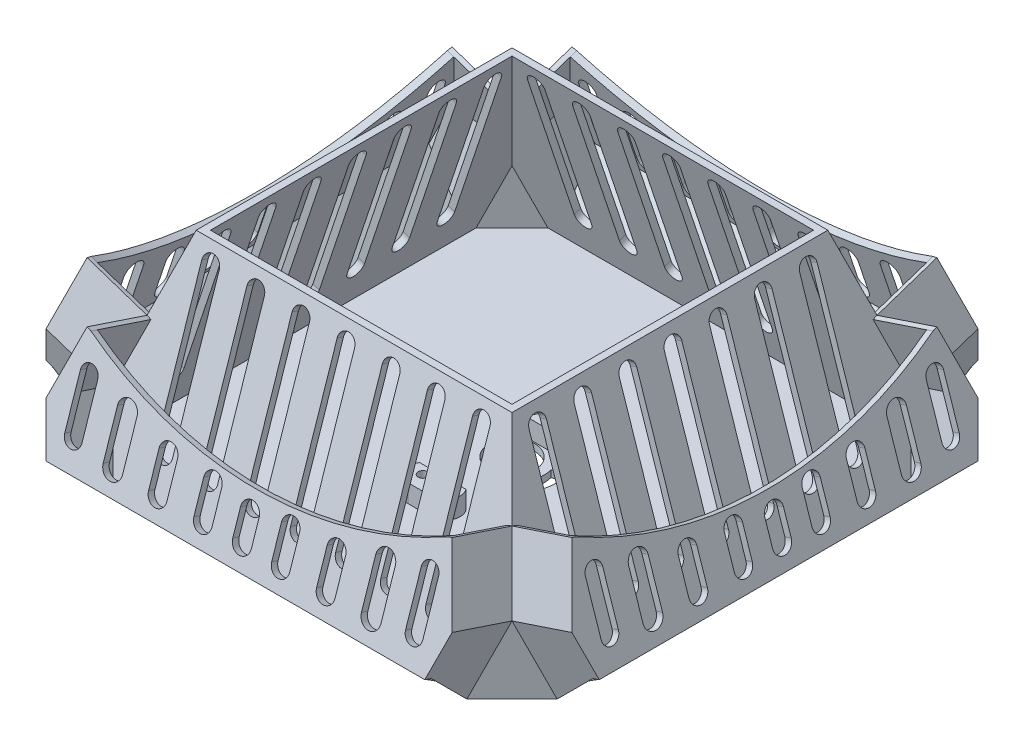
SolidWorks part; units mm, degrees
ref_plane "前视基准面" through (0, 0, 0) normal (0, 0, 1) x (1, 0, 0)
ref_plane "上视基准面" through (0, 0, 0) normal (0, 1, 0) x (1, 0, 0)
ref_plane "右视基准面" through (0, 0, 0) normal (1, 0, 0) x (0, 0, -1)
other "Configuration Table"
sketch "草图1" plane through (0, 0, 0) normal (0, 1, 0) x (1, 0, 0)
  line L1 (-70, 70) -> (70, 70)
  line L2 (-70, 70) -> (-70, -70)
  line L3 (-70, -70) -> (70, -70)
  line L4 (70, 70) -> (70, -70)
  line L5 (-70, 70) -> (70, -70) construction
  line L6 (-70, -70) -> (70, 70) construction
  point P0 (0, 0)
  dimension "D1" = 140
  dimension "D2" = 140
ref_plane "基准面1" through (0, -90, 0) normal (0, 1, 0) x (1, 0, 0)
sketch "草图2" plane through (0, -90, 0) normal (0, 1, 0) x (1, 0, 0)
  line L0 (70, 70) -> (70, -70) construction
  line L1 (-100, -100) -> (100, -100)
  line L2 (-100, -100) -> (-100, 100)
  line L3 (-100, 100) -> (100, 100)
  line L4 (100, -100) -> (100, 100)
  line L5 (-100, -100) -> (100, 100) construction
  line L6 (-100, 100) -> (100, -100) construction
  line L7 (-70, -70) -> (70, -70) construction
  point P0 (0, 0)
  dimension "D1" = 30
  dimension "D2" = 30
loft "放样1" add profiles "草图2", "草图1" connector at (-100, -90, -100) connector at (-70, 0, -70)
sketch "草图4" plane through (0, 0, 0) normal (0, 1, 0) x (1, 0, 0)
  line L0 (-80, 100) -> (-100, 80)
  line L1 (-100, 100) -> (100, 100) construction
  line L2 (-100, -100) -> (-100, 100) construction
  line L3 (-100, 80) -> (-100, 100)
  line L4 (-100, 100) -> (-80, 100)
  line L5 (100, 80) -> (80, 100)
  line L6 (80, 100) -> (100, 100)
  line L7 (100, 100) -> (100, 80)
  line L8 (80, -100) -> (100, -80)
  line L9 (100, -80) -> (100, -100)
  line L10 (100, -100) -> (80, -100)
  line L11 (-100, -80) -> (-80, -100)
  line L12 (-80, -100) -> (-100, -100)
  line L13 (-100, -100) -> (-100, -80)
  point P20 (0, 0)
  dimension "D1" = 45
  dimension "D2" = 20
  dimension "D3" = 4
extrude "切除-拉伸1" cut sketch "草图4" against normal blind 128
shell "抽壳2" thickness 3 removed face at (0, 0, 0)
sketch "草图6" plane through (0, 21, -63) normal (0, 0.3162, -0.9487) x (-1, 0, 0)
  line L0 (-90, -85.3815) -> (-80, -117.0043)
  line L1 (-80, -117.0043) -> (-76.8536, -117.0043)
  line L2 (-80, -117.0043) -> (80, -117.0043) construction
  line L3 (-76.8536, -117.0043) -> (-88.4268, -80.4066)
  line L4 (-90, -85.3815) -> (-70, -22.1359) construction
  line L5 (-88.4268, -80.4066) -> (-90, -85.3815)
  line L6 (90, -85.3815) -> (80, -117.0043)
  line L7 (80, -117.0043) -> (76.8536, -117.0043)
  line L8 (76.8536, -117.0043) -> (88.4268, -80.4066)
  line L9 (90, -85.3815) -> (70, -22.1359) construction
  line L10 (88.4268, -80.4066) -> (90, -85.3815)
  dimension "D1" = 3
  dimension "D2" = 3
extrude "凸台-拉伸1" add sketch "草图6" along normal blind 25
sketch "草图7" plane through (-63, 21, 0) normal (-0.9487, 0.3162, 0) x (0, 0, 1)
  line L0 (-80, -117.0043) -> (-90, -85.3815)
  line L1 (-90, -85.3815) -> (-88.4268, -80.4066)
  line L2 (-88.4268, -80.4066) -> (-70, -22.1359) construction
  line L3 (-88.4268, -80.4066) -> (-76.8536, -117.0043)
  line L4 (-80, -117.0043) -> (80, -117.0043) construction
  line L5 (-76.8536, -117.0043) -> (-80, -117.0043)
  line L6 (80, -117.0043) -> (90, -85.3815)
  line L7 (80, -117.0043) -> (90, -85.3815) construction
  line L8 (80, -117.0043) -> (100, -110.6797) construction
  line L9 (90, -85.3815) -> (100, -110.6797) construction
  line L10 (90, -85.3815) -> (88.4268, -80.4066)
  line L11 (90, -85.3815) -> (70, -22.1359) construction
  line L12 (88.4268, -80.4066) -> (76.8536, -117.0043)
  line L13 (76.8536, -117.0043) -> (80, -117.0043)
  dimension "D1" = 3
  dimension "D2" = 3
extrude "凸台-拉伸2" add sketch "草图7" along normal blind 25
sketch "草图8" plane through (0, 21, 63) normal (0, 0.3162, 0.9487) x (1, 0, 0)
  line L0 (-90, -85.3815) -> (-80, -117.0043)
  line L1 (-80, -117.0043) -> (-76.8536, -117.0043)
  line L2 (-80, -117.0043) -> (80, -117.0043) construction
  line L3 (-76.8536, -117.0043) -> (-88.4268, -80.4066)
  line L4 (-88.4268, -80.4066) -> (-70, -22.1359) construction
  line L5 (-88.4268, -80.4066) -> (-90, -85.3815)
  line L6 (90, -85.3815) -> (80, -117.0043)
  line L7 (80, -117.0043) -> (76.8536, -117.0043)
  line L8 (76.8536, -117.0043) -> (88.4268, -80.4066)
  line L9 (90, -85.3815) -> (70, -22.1359) construction
  line L10 (88.4268, -80.4066) -> (90, -85.3815)
  dimension "D1" = 3
  dimension "D2" = 3
extrude "凸台-拉伸3" add sketch "草图8" along normal blind 25
sketch "草图9" plane through (63, 21, 0) normal (0.9487, 0.3162, 0) x (0, 0, -1)
  line L0 (-90, -85.3815) -> (-80, -117.0043)
  line L1 (-80, -117.0043) -> (-76.8536, -117.0043)
  line L2 (-80, -117.0043) -> (80, -117.0043) construction
  line L3 (-76.8536, -117.0043) -> (-88.4268, -80.4066)
  line L4 (-88.4268, -80.4066) -> (-70, -22.1359) construction
  line L5 (-88.4268, -80.4066) -> (-90, -85.3815)
  line L6 (80, -117.0043) -> (90, -85.3815)
  line L7 (90, -85.3815) -> (88.4268, -80.4066)
  line L8 (88.4268, -80.4066) -> (70, -22.1359) construction
  line L9 (88.4268, -80.4066) -> (76.8536, -117.0043)
  line L10 (76.8536, -117.0043) -> (80, -117.0043)
  dimension "D1" = 3
  dimension "D2" = 3
extrude "凸台-拉伸4" add sketch "草图9" along normal blind 25
sketch "草图11" plane through (0, 0, 0) normal (0, 0, 1) x (1, 0, 0)
  line L0 (-100, -90) -> (-128.5669, -61.4331)
  line L1 (-128.5669, -61.4331) -> (-128.5669, -90)
  line L2 (110.0001, -90) -> (-110.0001, -90) construction
  line L3 (-128.5669, -90) -> (-100, -90)
  dimension "D1" = 45
extrude "切除-拉伸2" cut sketch "草图11" against normal mid plane 260
sketch "草图12" plane through (0, 0, 0) normal (1, 0, 0) x (0, 0, -1)
  line L0 (-100, -90) -> (-128.7607, -61.2393)
  line L1 (110.0001, -90) -> (-110.0001, -90) construction
  line L2 (-100, -90) -> (-90, -60) construction
  line L3 (-128.7607, -61.2393) -> (-128.7607, -90)
  line L4 (-128.7607, -90) -> (-100, -90)
  line L5 (0, 15.5887) -> (0, -110.0855) construction
  line L6 (128.7607, -90) -> (100, -90)
  line L7 (128.7607, -61.2393) -> (128.7607, -90)
  line L8 (100, -90) -> (128.7607, -61.2393)
  dimension "D1" = 45
extrude "切除-拉伸3" cut sketch "草图12" against normal mid plane 260
sketch "草图13" plane through (0, 0, 0) normal (0, 0, 1) x (1, 0, 0)
  line L0 (100, -90) -> (131.318, -58.682)
  line L1 (131.318, -58.682) -> (131.318, -90)
  line L2 (110.0001, -90) -> (-110.0001, -90) construction
  line L3 (131.318, -90) -> (100, -90)
  dimension "D1" = 45
extrude "切除-拉伸4" cut sketch "草图13" against normal mid plane 260
sketch "草图14" plane through (0, -87, 0) normal (0, 1, 0) x (1, 0, 0)
  circle A0 centre (0, 0) radius 3.5
  dimension "D1" = 7
extrude "切除-拉伸5" cut sketch "草图14" against normal mid plane 260
sketch "草图17" plane through (0, 0, 0) normal (1, 0, 0) x (0, 0, -1)
  line L0 (-119.7642, -70.2358) -> (-100, -90)
  line L1 (110.0001, -90) -> (-110.0001, -90) construction
  line L2 (-119.7642, -70.2358) -> (-100, -90) construction
  line L3 (-100, -90) -> (-98.9393, -86.818)
  line L4 (-100, -90) -> (-90, -60) construction
  line L5 (-98.9393, -86.818) -> (-118.7036, -67.0538)
  line L6 (-119.7642, -70.2358) -> (-113.7171, -52.0943) construction
  line L7 (-118.7036, -67.0538) -> (-119.7642, -70.2358)
  line L8 (0, 20.2497) -> (0, -104.6835) construction
  line L9 (118.7036, -67.0538) -> (119.7642, -70.2358)
  line L10 (98.9393, -86.818) -> (118.7036, -67.0538)
  line L11 (100, -90) -> (98.9393, -86.818)
  line L12 (119.7642, -70.2358) -> (100, -90)
  dimension "D1" = 3
extrude "凸台-拉伸8" add sketch "草图17" along normal up to next and the other way up to next
sketch "草图18" plane through (0, 0, 0) normal (0, 0, 1) x (1, 0, 0)
  line L0 (-119.7642, -70.2358) -> (-100, -90)
  line L1 (-100, -90) -> (-98.9393, -86.818)
  line L2 (-100, -90) -> (-90, -60) construction
  line L3 (-98.9393, -86.818) -> (-118.7036, -67.0538)
  line L4 (-119.7642, -70.2358) -> (-113.7171, -52.0943) construction
  line L5 (-118.7036, -67.0538) -> (-119.7642, -70.2358)
  line L6 (0, 15.1419) -> (0, -105.5441) construction
  line L7 (118.7036, -67.0538) -> (119.7642, -70.2358)
  line L8 (98.9393, -86.818) -> (118.7036, -67.0538)
  line L9 (100, -90) -> (98.9393, -86.818)
  line L10 (119.7642, -70.2358) -> (100, -90)
  dimension "D1" = 3
extrude "凸台-拉伸9" add sketch "草图18" along normal up to next and the other way up to next
sketch "草图20" plane through (0, -87, 0) normal (0, 1, 0) x (1, 0, 0)
  circle A0 centre (0, 0) radius 10.1
  dimension "D1" = 20.2
extrude "切除-拉伸6" cut sketch "草图20" against normal blind 26
sketch "草图22" plane through (63, 21, 0) normal (0.9487, 0.3162, 0) x (0, 0, -1)
  line L0 (-61.1056, -30.1412) -> (-61.1056, -95.5093) construction
  line L1 (-57.2442, -30.1412) -> (-57.2442, -95.5093)
  line L2 (-64.967, -30.1412) -> (-64.967, -95.5093)
  line L3 (-41.1056, -30.1412) -> (-41.1056, -95.5093) construction
  line L4 (-37.2442, -30.1412) -> (-37.2442, -95.5093)
  line L5 (-44.967, -30.1412) -> (-44.967, -95.5093)
  line L6 (-21.1056, -30.1412) -> (-21.1056, -95.5093) construction
  line L7 (-17.2442, -30.1412) -> (-17.2442, -95.5093)
  line L8 (-24.967, -30.1412) -> (-24.967, -95.5093)
  line L9 (-1.1056, -30.1412) -> (-1.1056, -95.5093) construction
  line L10 (2.7558, -30.1412) -> (2.7558, -95.5093)
  line L11 (-4.967, -30.1412) -> (-4.967, -95.5093)
  line L12 (18.8944, -30.1412) -> (18.8944, -95.5093) construction
  line L13 (22.7558, -30.1412) -> (22.7558, -95.5093)
  line L14 (15.033, -30.1412) -> (15.033, -95.5093)
  line L15 (38.8944, -30.1412) -> (38.8944, -95.5093) construction
  line L16 (42.7558, -30.1412) -> (42.7558, -95.5093)
  line L17 (35.033, -30.1412) -> (35.033, -95.5093)
  line L18 (58.8944, -30.1412) -> (58.8944, -95.5093) construction
  line L19 (62.7558, -30.1412) -> (62.7558, -95.5093)
  line L20 (55.033, -30.1412) -> (55.033, -95.5093)
  arc A0 (-57.2442, -30.1412) -> (-64.967, -30.1412) centre (-61.1056, -30.1412) ccw
  arc A1 (-64.967, -95.5093) -> (-57.2442, -95.5093) centre (-61.1056, -95.5093) ccw
  arc A2 (-37.2442, -30.1412) -> (-44.967, -30.1412) centre (-41.1056, -30.1412) ccw
  arc A3 (-44.967, -95.5093) -> (-37.2442, -95.5093) centre (-41.1056, -95.5093) ccw
  arc A4 (-17.2442, -30.1412) -> (-24.967, -30.1412) centre (-21.1056, -30.1412) ccw
  arc A5 (-24.967, -95.5093) -> (-17.2442, -95.5093) centre (-21.1056, -95.5093) ccw
  arc A6 (2.7558, -30.1412) -> (-4.967, -30.1412) centre (-1.1056, -30.1412) ccw
  arc A7 (-4.967, -95.5093) -> (2.7558, -95.5093) centre (-1.1056, -95.5093) ccw
  arc A8 (22.7558, -30.1412) -> (15.033, -30.1412) centre (18.8944, -30.1412) ccw
  arc A9 (15.033, -95.5093) -> (22.7558, -95.5093) centre (18.8944, -95.5093) ccw
  arc A10 (42.7558, -30.1412) -> (35.033, -30.1412) centre (38.8944, -30.1412) ccw
  arc A11 (35.033, -95.5093) -> (42.7558, -95.5093) centre (38.8944, -95.5093) ccw
  arc A12 (62.7558, -30.1412) -> (55.033, -30.1412) centre (58.8944, -30.1412) ccw
  arc A13 (55.033, -95.5093) -> (62.7558, -95.5093) centre (58.8944, -95.5093) ccw
  point P2 (-61.1056, -62.8252)
  point P11 (-41.1056, -62.8252)
  point P18 (-21.1056, -62.8252)
  point P25 (-1.1056, -62.8252)
  point P32 (18.8944, -62.8252)
  point P39 (38.8944, -62.8252)
  point P46 (58.8944, -62.8252)
  dimension "D1" = 7
extrude "切除-拉伸7" cut sketch "草图22" against normal blind 10
pattern_circular "阵列(圆周)2" count 4 every 90 about axis through (0, -87, 0) along (0, 1, 0) of "切除-拉伸7"
sketch "草图26" plane through (0, -87, 0) normal (0, 1, 0) x (1, 0, 0)
  circle A0 centre (-5, 14.5) radius 2.1
  circle A1 centre (5, 14.5) radius 2.1
  circle A2 centre (-5, -34.5) radius 2.1
  circle A3 centre (5, -34.5) radius 2.1
  dimension "D1" = 4.2
extrude "切除-拉伸10" cut sketch "草图26" against normal blind 10
sketch "草图37" plane through (0, -90, 0) normal (0, -1, 0) x (1, 0, 0)
  circle A0 centre (0, 0) radius 32.5
  circle A1 centre (0, 0) radius 45
  dimension "D1" = 65
  dimension "D2" = 90
extrude "切除-拉伸13" cut sketch "草图37" against normal blind 1
sketch "草图51" plane through (0, -90, 0) normal (0, -1, 0) x (1, 0, 0)
  line L2 (11.2742, 8.4827) -> (15.9244, 11.9814)
  line L3 (13.6163, -3.696) -> (19.2324, -5.2205)
  arc A2 (13.6163, -3.696) -> (11.2742, 8.4827) centre (0, 0) ccw
  arc A3 (19.2324, -5.2205) -> (15.9244, 11.9814) centre (0, 0) ccw
extrude "切除-拉伸14" cut sketch "草图51" against normal blind 10
sketch "草图53" plane through (0, -87, 0) normal (0, 1, 0) x (1, 0, 0)
  line L0 (-5, 14.5) -> (5, 14.5) construction
  line L1 (-5, 21) -> (5, 21)
  line L2 (-5, 8) -> (5, 8)
  line L3 (-5, -34.5) -> (5, -34.5) construction
  line L4 (-5, -28) -> (5, -28)
  line L5 (-5, -41) -> (5, -41)
  arc A0 (-5, 21) -> (-5, 8) centre (-5, 14.5) ccw
  arc A1 (5, 8) -> (5, 21) centre (5, 14.5) ccw
  arc A2 (-5, -28) -> (-5, -41) centre (-5, -34.5) ccw
  arc A3 (5, -41) -> (5, -28) centre (5, -34.5) ccw
  point P4 (0, 14.5)
  point P9 (0, -34.5)
  dimension "D1" = 13
  dimension "D2" = 13
extrude "凸台-拉伸17" add sketch "草图53" along normal blind 8
sketch "草图54" plane through (0, -90, 0) normal (0, -1, 0) x (1, 0, 0)
  circle A0 centre (-5, -14.5) radius 2.1
  circle A1 centre (5, -14.5) radius 2.1
  circle A2 centre (0, 0) radius 10.1
  circle A3 centre (-5, 34.5) radius 2.1
  circle A4 centre (5, 34.5) radius 2.1
extrude "切除-拉伸15" cut sketch "草图54" against normal blind 160
sketch "草图55" plane through (0, -87, 0) normal (0, 1, 0) x (1, 0, 0)
  line L0 (-18.9185, 0) -> (-18.9185, 10.5924)
  line L2 (-18.9185, 0) -> (-18.9185, -30.6798)
  line L3 (-18.9185, -30.6798) -> (17.5542, -30.6798)
  line L4 (17.5542, 0) -> (17.5542, -30.6798)
  line L5 (-18.9185, 10.5924) -> (17.5542, 10.5924)
  line L6 (17.5542, 10.5924) -> (17.5542, 0)
extrude "切除-拉伸16" cut sketch "草图55" along normal blind 160
pattern_circular "阵列(圆周)3" count 4 every 90 about axis through (0, -113, 0) along (0, 1, 0) of "凸台-拉伸8"
sketch "草图57" plane through (-63, 21, 0) normal (-0.9487, 0.3162, 0) x (0, 0, 1)
  line L0 (-88.4268, -80.4066) -> (-80.889, -56.57)
  line L1 (-88.4268, -80.4066) -> (-70, -22.1359) construction
  line L2 (-80.889, -56.57) -> (-78.9821, -57.173)
  line L3 (-78.9821, -57.173) -> (-87.378, -83.7232)
  line L4 (-77.9142, -113.6502) -> (-88.4268, -80.4066) construction
  line L5 (-88.4268, -80.4066) -> (-87.378, -83.7232)
  line L6 (0, -117.0043) -> (0, 49.8751) construction
  line L8 (-76.8536, -117.0043) -> (76.8536, -117.0043) construction
  line L9 (88.4268, -80.4066) -> (87.378, -83.7232)
  line L10 (78.9821, -57.173) -> (87.378, -83.7232)
  line L11 (80.889, -56.57) -> (78.9821, -57.173)
  line L12 (88.4268, -80.4066) -> (80.889, -56.57)
  dimension "D1" = 2
  dimension "D2" = 25
extrude "凸台-拉伸22" add sketch "草图57" along normal blind 25
pattern_circular "阵列(圆周)4" count 4 every 90 about axis through (0, -113, 0) along (0, 1, 0) of "凸台-拉伸22"
sketch "草图58" plane through (0, 28.9057, 86.7171) normal (0, 0.3162, 0.9487) x (1, 0, 0)
  line L0 (-80.889, -56.57) -> (-90, -85.3815)
  line L1 (-90, -85.3815) -> (-83.9528, -104.5043)
  line L2 (-83.9528, -104.5043) -> (83.9528, -104.5043)
  line L3 (83.9528, -104.5043) -> (90, -85.3815)
  line L4 (90, -85.3815) -> (80.889, -56.57)
  line L5 (80.889, -56.57) -> (78.9821, -57.173)
  line L6 (-80.889, -56.57) -> (-78.9821, -57.173)
  line L7 (0, -104.5043) -> (0, -58.3989) construction
  line L8 (0, -84.2936) -> (0, -95.1298) construction
  line L9 (4.1281, -84.2936) -> (4.1281, -95.1298)
  line L10 (-4.1281, -84.2936) -> (-4.1281, -95.1298)
  line L11 (-17.2442, -81.7439) -> (-17.2442, -95.5093) construction
  line L12 (-17.2442, -95.5093) -> (-17.2442, -30.1412) construction
  line L13 (-13.2418, -81.7439) -> (-13.2418, -95.5093)
  line L14 (-21.2466, -81.7439) -> (-21.2466, -95.5093)
  line L15 (-37.2442, -80.7877) -> (-37.2442, -95.5093) construction
  line L16 (-37.2442, -95.5093) -> (-37.2442, -30.1412) construction
  line L17 (-33.1614, -80.7877) -> (-33.1614, -95.5093)
  line L18 (-41.327, -80.7877) -> (-41.327, -95.5093)
  line L19 (-57.2442, -75.0509) -> (-57.2442, -95.1298) construction
  line L20 (-57.2442, -95.5093) -> (-57.2442, -30.1412) construction
  line L21 (-52.9216, -75.0509) -> (-52.9216, -95.1298)
  line L22 (-61.5667, -75.0509) -> (-61.5667, -95.1298)
  line L23 (-75.5503, -70.7283) -> (-75.5503, -92.7395) construction
  line L24 (-71.7257, -70.7283) -> (-71.7257, -92.7395)
  line L25 (-79.3749, -70.7283) -> (-79.3749, -92.7395)
  line L26 (75.5503, -70.7283) -> (75.5503, -92.7395) construction
  line L27 (71.7257, -70.7283) -> (71.7257, -92.7395)
  line L28 (79.3749, -70.7283) -> (79.3749, -92.7395)
  line L29 (57.2442, -75.0509) -> (57.2442, -95.1298) construction
  line L30 (52.9216, -75.0509) -> (52.9216, -95.1298)
  line L31 (61.5667, -75.0509) -> (61.5667, -95.1298)
  line L32 (37.2442, -80.7877) -> (37.2442, -95.5093) construction
  line L33 (33.1614, -80.7877) -> (33.1614, -95.5093)
  line L34 (41.327, -80.7877) -> (41.327, -95.5093)
  line L35 (17.2442, -81.7439) -> (17.2442, -95.5093) construction
  line L36 (13.2418, -81.7439) -> (13.2418, -95.5093)
  line L37 (21.2466, -81.7439) -> (21.2466, -95.5093)
  arc A0 (-78.9821, -57.173) -> (78.9821, -57.173) centre (0, 97.3143) ccw
  arc A1 (4.1281, -84.2936) -> (-4.1281, -84.2936) centre (0, -84.2936) ccw
  arc A2 (-4.1281, -95.1298) -> (4.1281, -95.1298) centre (0, -95.1298) ccw
  arc A3 (-13.2418, -81.7439) -> (-21.2466, -81.7439) centre (-17.2442, -81.7439) ccw
  arc A4 (-21.2466, -95.5093) -> (-13.2418, -95.5093) centre (-17.2442, -95.5093) ccw
  arc A5 (-33.1614, -80.7877) -> (-41.327, -80.7877) centre (-37.2442, -80.7877) ccw
  arc A6 (-41.327, -95.5093) -> (-33.1614, -95.5093) centre (-37.2442, -95.5093) ccw
  arc A7 (-52.9216, -75.0509) -> (-61.5667, -75.0509) centre (-57.2442, -75.0509) ccw
  arc A8 (-61.5667, -95.1298) -> (-52.9216, -95.1298) centre (-57.2442, -95.1298) ccw
  arc A9 (-71.7257, -70.7283) -> (-79.3749, -70.7283) centre (-75.5503, -70.7283) ccw
  arc A10 (-79.3749, -92.7395) -> (-71.7257, -92.7395) centre (-75.5503, -92.7395) ccw
  arc A11 (71.7257, -70.7283) -> (79.3749, -70.7283) centre (75.5503, -70.7283) cw
  arc A12 (79.3749, -92.7395) -> (71.7257, -92.7395) centre (75.5503, -92.7395) cw
  arc A13 (52.9216, -75.0509) -> (61.5667, -75.0509) centre (57.2442, -75.0509) cw
  arc A14 (61.5667, -95.1298) -> (52.9216, -95.1298) centre (57.2442, -95.1298) cw
  arc A15 (33.1614, -80.7877) -> (41.327, -80.7877) centre (37.2442, -80.7877) cw
  arc A16 (41.327, -95.5093) -> (33.1614, -95.5093) centre (37.2442, -95.5093) cw
  arc A17 (13.2418, -81.7439) -> (21.2466, -81.7439) centre (17.2442, -81.7439) cw
  arc A18 (21.2466, -95.5093) -> (13.2418, -95.5093) centre (17.2442, -95.5093) cw
  point P20 (0, -89.7117)
  point P27 (-17.2442, -88.6266)
  point P36 (-37.2442, -88.1485)
  point P45 (-57.2442, -85.0904)
  point P54 (-75.5503, -81.7339)
  point P63 (75.5503, -81.7339)
  point P70 (57.2442, -85.0904)
  point P77 (37.2442, -88.1485)
  point P84 (17.2442, -88.6266)
extrude "凸台-拉伸24" add sketch "草图58" along normal blind 3 contours A0 L5 L4 L3 L2 L1 L0 L6 | L25 A10 L24 A9 | L22 A8 L21 A7 | L18 A6 L17 A5 | L13 A4 L14 A3 | L10 A2 L9 A1 | L36 A18 L37 A17 | L33 A16 L34 A15 | L30 A14 L31 A13 | L27 A12 L28 A11
pattern_circular "阵列(圆周)5" count 4 every 90 about axis through (0, -113, 0) along (0, 1, 0) of "凸台-拉伸24"
sketch "草图60" plane through (0, 0, 0) normal (1, 0, 0) x (0, 0, -1)
  line L0 (122.6103, -69.2871) -> (117.4068, -72.5932)
  line L1 (100, -90) -> (119.7642, -70.2358) construction
  line L2 (117.4068, -72.5932) -> (119.7642, -70.2358)
  line L3 (119.7642, -70.2358) -> (122.6103, -69.2871)
extrude "凸台-拉伸25" add sketch "草图60" along normal mid plane 167
pattern_circular "阵列(圆周)6" count 4 every 90 about axis through (0, -113, 0) along (0, 1, 0) of "凸台-拉伸25"
